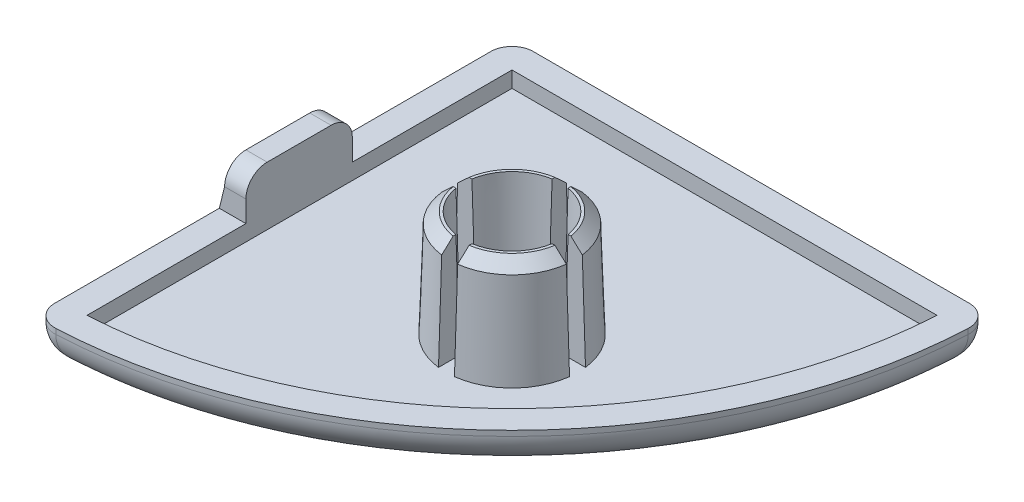
SolidWorks part; units mm, degrees
ref_plane "前视" through (0, 0, 0) normal (0, 0, 1) x (1, 0, 0)
ref_plane "上视" through (0, 0, 0) normal (0, 1, 0) x (1, 0, 0)
ref_plane "右视" through (0, 0, 0) normal (1, 0, 0) x (0, 0, -1)
sketch "草图1" plane through (0, 0, 0) normal (0, 1, 0) x (1, 0, 0)
  line L2 (-22.5, -22.5) -> (-22.5, 22.5)
  line L3 (-22.5, 22.5) -> (22.5, 22.5)
  line L5 (-22.5, -22.5) -> (22.5, 22.5) construction
  line L6 (-22.5, 22.5) -> (5.0045, -5.0045) construction
  arc A0 (-22.5, -22.5) -> (22.5, 22.5) centre (-22.5, 22.5) ccw
  point P0 (0, 0)
  dimension "D2" = 45
extrude "凸台-拉伸1" add sketch "草图1" along normal blind 3.5
sketch "草图2" plane through (0, 3.5, 0) normal (0, 1, 0) x (1, 0, 0)
  line L6 (19.9264, 20) -> (-20, 20)
  line L7 (-20, 20) -> (-20, -19.9264)
  line L8 (19.9264, 20) -> (-20, 20)
  line L9 (-20, 20) -> (-20, -19.9264)
  arc A3 (-20, -19.9264) -> (19.9264, 20) centre (-22.5, 22.5) ccw
  arc A4 (-20, -19.9264) -> (19.9264, 20) centre (-22.5, 22.5) ccw
  dimension "D1" = 2.5
extrude "切除-拉伸1" cut sketch "草图2" against normal blind 1.5
fillet "圆角1" radius 2 3 edges at (-22.5, 1.75, -22.5) (-22.5, 1.75, 22.5) (22.5, 1.75, -22.5)
fillet "圆角2" radius 3 6 edges at (-0.0233, 0, -22.5) (-21.9142, 0, -21.9142) (-22.5, 0, -0.0233) (9.3198, 0, 9.3198) (21.9002, 0, -21.8809) (-21.8809, 0, 21.9002)
sketch "草图3" plane through (0, 3.5, 0) normal (0, 1, 0) x (1, 0, 0)
  line L1 (-22, 5) -> (-20, 5)
  line L2 (-22, 5) -> (-22, -5)
  line L3 (-22, -5) -> (-20, -5)
  line L4 (-20, 5) -> (-20, -5)
  dimension "D2" = 10
  dimension "D3" = 2
extrude "凸台-拉伸2" add sketch "草图3" along normal blind 4
sketch "草图5" plane through (0, 0, 5) normal (0, 0, 1) x (1, 0, 0)
  line L0 (-22, 7.5) -> (-22, 3.5) construction
  line L1 (-22.5, 3.5) -> (-22, 3.5)
  line L4 (-22, 3.5) -> (-22, 5.5)
  line L5 (-22, 5.5) -> (-22.5, 3.5)
extrude "凸台-拉伸3" add sketch "草图5" against normal up to surface (10 mm away) up to face at (-20.75, 6, -5)
sketch "草图6" plane through (0, 2, 0) normal (0, 1, 0) x (1, 0, 0)
  circle A0 centre (0, 0) radius 6.2
  circle A1 centre (0, 0) radius 4.25
  dimension "D1" = 12.4
  dimension "D2" = 8.5
extrude "凸台-拉伸4" add sketch "草图6" along normal blind 10 draft 1.88
chamfer "倒角1" distance 1 angle 45 1 edges at (0, 12, 5.8718) first distance on face at (0, 12, 5.8718)
sketch "草图7" plane through (0, 12, 0) normal (0, 1, 0) x (1, 0, 0)
  line L1 (-0.75, -8.4649) -> (0.75, -8.4649)
  line L2 (-0.75, -8.4649) -> (-0.75, -0.75)
  line L3 (-0.75, 8.4649) -> (0.75, 8.4649)
  line L4 (0.75, -8.4649) -> (0.75, -0.75)
  line L7 (-8.6795, 0.75) -> (-0.75, 0.75)
  line L8 (-8.6795, 0.75) -> (-8.6795, -0.75)
  line L9 (-8.6795, -0.75) -> (-0.75, -0.75)
  line L10 (8.6795, 0.75) -> (8.6795, -0.75)
  line L13 (-0.75, 0.75) -> (-0.75, 8.4649)
  line L17 (0.75, 0.75) -> (0.75, 8.4649)
  line L19 (0.75, 0.75) -> (8.6795, 0.75)
  line L20 (0.75, -0.75) -> (8.6795, -0.75)
  point P0 (0, 0)
  point P6 (0, 0)
  dimension "D1" = 1.5
  dimension "D2" = 1.5
extrude "切除-拉伸2" cut sketch "草图7" against normal up to surface (10 mm away) up to face at (-4.1616, 2, -4.1616)
fillet "圆角3" radius 2 2 edges at (-21, 7.5, -5) (-21, 7.5, 5)
